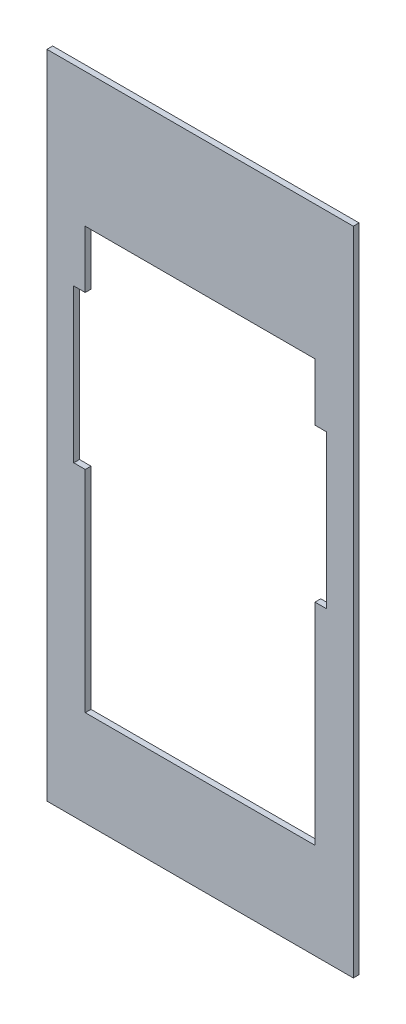
SolidWorks part; units mm, degrees
ref_plane "Front Plane" through (0, 0, 0) normal (0, 0, 1) x (1, 0, 0)
ref_plane "Top Plane" through (0, 0, 0) normal (0, 1, 0) x (1, 0, 0)
ref_plane "Right Plane" through (0, 0, 0) normal (1, 0, 0) x (0, 0, -1)
sketch "Sketch1" plane through (0, 0, 0) normal (0, 0, 1) x (1, 0, 0)
  line L1 (40, 85) -> (-40, 85)
  line L2 (40, 85) -> (40, -85)
  line L3 (40, -85) -> (-40, -85)
  line L4 (-40, 85) -> (-40, -85)
  line L5 (40, 85) -> (-40, -85) construction
  line L6 (40, -85) -> (-40, 85) construction
  line L20 (0, 0) -> (0, 85) construction
  line L21 (0, 0) -> (0, -85) construction
  line L23 (30, 50) -> (-30, 50)
  line L26 (-30, 50) -> (-30, 35)
  line L27 (-30, -60) -> (30, -60)
  line L33 (-30, 35) -> (-33, 35)
  line L35 (-30, -5) -> (-33, -5)
  line L36 (-33, 35) -> (-33, -5)
  line L37 (-30, -5) -> (-30, -60)
  line L38 (30, -5) -> (30, -60)
  line L39 (30, -5) -> (33, -5)
  line L40 (33, 35) -> (33, -5)
  line L41 (30, 35) -> (33, 35)
  line L42 (30, 50) -> (30, 35)
  point P0 (0, 0)
  dimension "D2" = 3
  dimension "D3" = 10
  dimension "D4" = 55
  dimension "D5" = 170
  dimension "D6" = 35
  dimension "D7" = 40
  dimension "D8" = 40
  dimension "D11" = 15
extrude "Boss-Extrude1" add sketch "Sketch1" along normal blind 1.5
